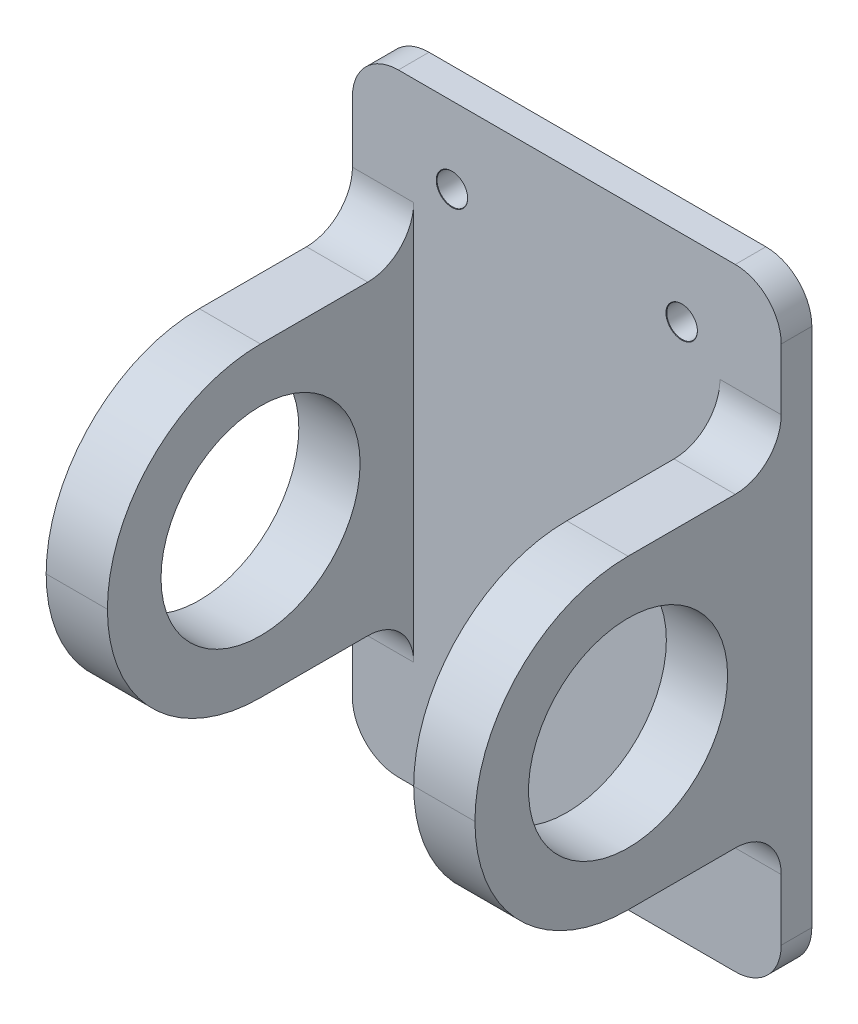
SolidWorks part; units mm, degrees
material "Rubber"
ref_plane "Front Plane" through (0, 0, 0) normal (1, 0, 0) x (0, 1, 0)
ref_plane "Top Plane" through (0, 0, 0) normal (0, 0, 1) x (0, 1, 0)
ref_plane "Right Plane" through (0, 0, 0) normal (0, 1, 0) x (-1, 0, 0)
sketch "Sketch1" plane through (0, 0, 0) normal (0, 0, 1) x (0, 1, 0)
  line L1 (-20, 14) -> (20, 14)
  line L2 (-20, 14) -> (-20, -14)
  line L3 (-20, -14) -> (20, -14)
  line L4 (20, 14) -> (20, -14)
  point P4 (0, 14)
  point P6 (-20, 0)
  dimension "D1" = 0
  dimension "D2" = 0
  dimension "D3" = 28
  dimension "D4" = 40
extrude "Boss-Extrude1" add sketch "Sketch1" against normal blind 2
sketch "Sketch2" plane through (0, 0, 0) normal (0, 0, 1) x (0, 1, 0)
  line L1 (-10, 14) -> (10, 14)
  line L2 (-10, 14) -> (-10, -14)
  line L3 (-10, -14) -> (10, -14)
  line L4 (-20, 14) -> (-20, -14)
  line L5 (-20, -14) -> (20, -14)
  line L6 (20, -14) -> (20, 14)
  line L7 (20, 14) -> (-20, 14)
  line L8 (-20, 14) -> (-20, -14)
  line L9 (-20, -14) -> (20, -14)
  line L10 (20, -14) -> (20, 14)
  line L11 (20, 14) -> (-20, 14)
  line L12 (10, 14) -> (10, -14)
  line L13 (-10, 10) -> (10, 10)
  line L14 (-10, 10) -> (-10, -10)
  line L15 (-10, -10) -> (10, -10)
  line L16 (10, 10) -> (10, -10)
  point P8 (0, 14)
  point P9 (0, 14)
  point P14 (-10, 0)
  point P15 (-10, 0)
  dimension "D2" = 0
  dimension "D3" = 20
  dimension "D4" = 0
  dimension "D5" = 20
  dimension "D1" = 0
extrude "Boss-Extrude2" add sketch "Sketch2" along normal blind 20 contours L2 L13 L12 L1 | L15 L2 L3 L12 region at (-12, 0, 0) region at (12, 0, 0)
fillet "Fillet1" radius 10 4 edges at (12, 10, 20) (12, -10, 20) (-12, 10, 20) (-12, -10, 20)
sketch "Sketch3" plane through (14, 0, 0) normal (1, 0, 0) x (0, 1, 0)
  line L7 (10, 0) -> (10, 10)
  line L8 (-10, 10) -> (-10, 0)
  line L9 (-10, 0) -> (-20, 0)
  line L10 (-20, 0) -> (-20, -2)
  line L11 (-20, -2) -> (20, -2)
  line L12 (20, -2) -> (20, 0)
  line L13 (20, 0) -> (10, 0)
  line L14 (10, 0) -> (10, 10)
  line L15 (-10, 10) -> (-10, 0)
  line L16 (-10, 0) -> (-20, 0)
  line L17 (-20, 0) -> (-20, -2)
  line L18 (-20, -2) -> (20, -2)
  line L19 (20, -2) -> (20, 0)
  line L20 (20, 0) -> (10, 0)
  arc A2 (10, 10) -> (0, 20) centre (0, 10) ccw
  arc A3 (0, 20) -> (-10, 10) centre (0, 10) ccw
  arc A4 (10, 10) -> (0, 20) centre (0, 10) ccw
  arc A5 (0, 20) -> (-10, 10) centre (0, 10) ccw
  point P5 (0, 10)
  dimension "D1" = 0
hole_wizard "Ø10.0mm Dowel Hole1" positions "Sketch3" profile "Sketch4" hole size "Ø10.0" standard "IS" end condition through all
sketch "Sketch4" plane through (14, 0, 10) normal (0, 1, 0) x (0, 0, -1)
  line L0 (0, 0) -> (0, 28)
  line L1 (0, 28) -> (6.5, 28)
  line L2 (6.5, 28) -> (6.5, 0)
  line L5 (6.5, 0) -> (0, 0)
  line L11 (0, -6.35) -> (0, 107.95) construction
  dimension "Thru Hole Dia." = 13
  dimension "Thru Hole Depth" = 28
sketch "Sketch5" plane through (0, 0, 0) normal (0, 0, 1) x (0, 1, 0)
  line L1 (-15, -7.5) -> (15, -7.5)
  line L2 (-15, -7.5) -> (-15, 7.5)
  line L3 (-15, 7.5) -> (15, 7.5)
  line L4 (15, -7.5) -> (15, 7.5)
  point P4 (-15, 0)
  point P6 (0, 7.5)
  point P8 (-15, 7.5)
  point P9 (-15, -7.5)
  point P10 (15, 7.5)
  point P11 (15, -7.5)
  dimension "D1" = 0
  dimension "D2" = 0
  dimension "D3" = 30
  dimension "D4" = 15
hole_wizard "Ø2.0mm Dowel Hole1" positions "Sketch5" profile "Sketch6" hole size "Ø2.0" standard "IS" end condition through all
sketch "Sketch6" plane through (7.5, 15, 0) normal (1, 0, 0) x (0, -1, 0)
  line L0 (0, 0) -> (0, 2)
  line L1 (0, 2) -> (1, 2)
  line L2 (1, 2) -> (1, 0.025)
  line L3 (1, 0.025) -> (1.025, 0)
  line L5 (1.025, 0) -> (0, 0)
  line L6 (-1, 0.025) -> (-1.025, 0) construction
  line L11 (0, -6.35) -> (0, 107.95) construction
  dimension "Thru Hole Dia." = 2
  dimension "Thru Hole Depth" = 2
  dimension "Near C'Sink Dia." = 2.05
  dimension "Near C'Sink Angle" = 90
fillet "Fillet2" radius 3 8 edges at (12, 10, 0) (-12, 10, 0) (12, -10, 0) (-12, -10, 0) (-14, -20, -1) (-14, 20, -1) (14, 20, -1) (14, -20, -1)
